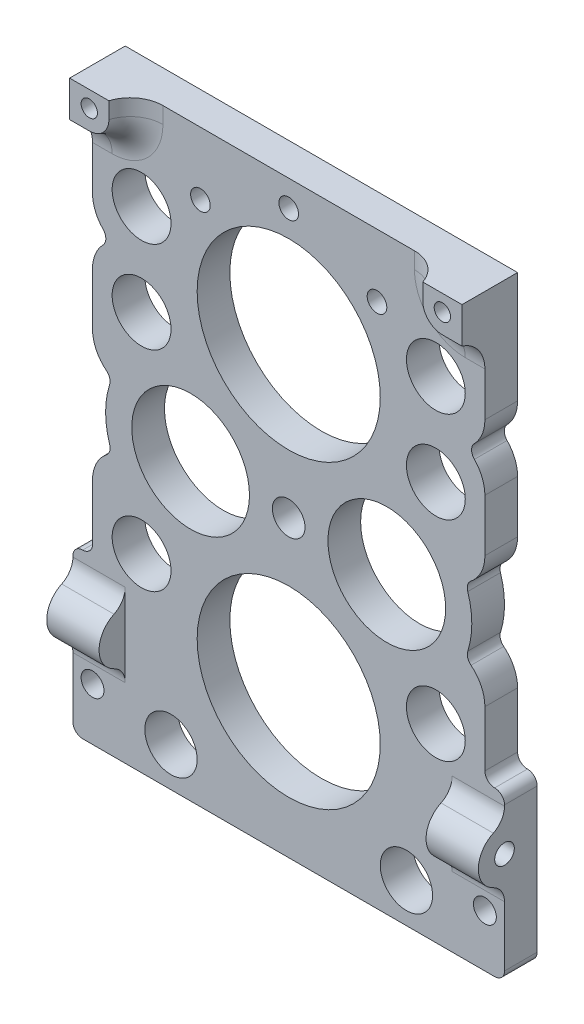
SolidWorks part; units mm, degrees
ref_plane "Front Plane" through (0, 0, 0) normal (0, 0, 1) x (1, 0, 0)
ref_plane "Top Plane" through (0, 0, 0) normal (0, 1, 0) x (1, 0, 0)
ref_plane "Right Plane" through (0, 0, 0) normal (1, 0, 0) x (0, 0, -1)
sketch "Sketch1" plane through (0, 0, 0) normal (0, 0, 1) x (1, 0, 0)
  line L1 (30, 45) -> (-30, 45)
  line L2 (30, 45) -> (30, -45)
  line L3 (30, -45) -> (-30, -45)
  line L4 (-30, 45) -> (-30, -45)
  line L5 (30, 45) -> (-30, -45) construction
  line L6 (30, -45) -> (-30, 45) construction
  point P0 (0, 0)
  dimension "D1" = 60
  dimension "D2" = 90
extrude "Boss-Extrude1" add sketch "Sketch1" along normal blind 5
sketch "Sketch2" plane through (30, 0, 0) normal (1, 0, 0) x (0, 0, -1)
  line L0 (0, -45) -> (0, 45) construction
  line L1 (-5, -45) -> (0, -45)
  line L2 (-5, -45) -> (-5, -20)
  line L3 (-5, -20) -> (0, -20)
  line L4 (0, -45) -> (0, -20)
  dimension "D1" = 25
extrude "Boss-Extrude2" add sketch "Sketch2" along normal blind 3
mirror "Mirror1" about plane through (0, 0, 0) normal (1, 0, 0) of "Boss-Extrude2"
sketch "Sketch3" plane through (0, 0, 5) normal (0, 0, 1) x (1, 0, 0)
  line L0 (0, 0) -> (0, 50000) construction
  line L1 (22.5, 13.0684) -> (22.5, -49986.9316) construction
  line L2 (-22.5, 11.0527) -> (-22.5, -49988.9473) construction
  line L3 (-15, 13.2998) -> (-15, -49986.7002) construction
  line L4 (15, 12.7972) -> (15, -49987.2028) construction
  line L5 (-1.6097, 0) -> (49998.3903, 0) construction
  line L6 (-5.4322, 16) -> (49994.5678, 16) construction
  line L7 (-7.793, 30) -> (49992.207, 30) construction
  line L8 (-33, -45) -> (33, -45) construction
  line L12 (0, 23) -> (-50000, 23) construction
  line L16 (30, -20) -> (30, 45) construction
  line L17 (30, -10) -> (30, 10)
  line L18 (30, 18) -> (30, 28)
  line L19 (27, 23) -> (27, -49977) construction
  line L21 (-30, 18) -> (-30, 28)
  line L22 (-30, -10) -> (-30, 10)
  circle A0 centre (0, -23) radius 14
  circle A1 centre (0, 23) radius 14
  circle A2 centre (15, 0) radius 9
  circle A3 centre (-15, 0) radius 9
  circle A4 centre (-22.5, -16) radius 4.5
  circle A5 centre (-18, -39) radius 4
  circle A6 centre (22.5, -16) radius 4.5
  circle A7 centre (18, -39) radius 4
  circle A10 centre (22.5, 16) radius 4.5
  circle A11 centre (22.5, 30) radius 4.5
  circle A12 centre (-22.5, 30) radius 4.5
  circle A13 centre (-22.5, 16) radius 4.5
  circle A14 centre (0, 0) radius 2.5
  arc A15 (30, 28) -> (27, 23) centre (24.3333, 28) cw
  arc A16 (30, 18) -> (27, 23) centre (24.3333, 18) ccw
  arc A17 (30, 10) -> (27, 5) centre (24.3333, 10) cw
  arc A18 (30, -10) -> (27, -5) centre (24.3333, -10) ccw
  arc A21 (27, -5) -> (27, 5) centre (15, 0) ccw
  arc A24 (-30, 28) -> (-27, 23) centre (-24.3333, 28) ccw
  arc A25 (-30, 18) -> (-27, 23) centre (-24.3333, 18) cw
  arc A26 (-30, -10) -> (-27, -5) centre (-24.3333, -10) cw
  arc A27 (-30, 10) -> (-27, 5) centre (-24.3333, 10) ccw
  arc A28 (-27, -5) -> (-27, 5) centre (-15, 0) cw
  point P3 (0, 0)
  dimension "D1" = 28
  dimension "D4" = 18
  dimension "D5" = 9
  dimension "D7" = 6
  dimension "D12" = 5
  dimension "D15" = 3
  dimension "D16" = 10
  dimension "D8" = 8
  dimension "D2" = 16
  dimension "D3" = 30
  dimension "D6" = 45
  dimension "D9" = 14
  dimension "D10" = 36
  dimension "D13" = 10
  dimension "D14" = 20
extrude "Cut-Extrude1" cut sketch "Sketch3" against normal through all
sketch "Sketch4" plane through (0, 0, 5) normal (0, 0, 1) x (1, 0, 0)
  line L0 (-33, -45) -> (33, -45) construction
  line L1 (0, 0) -> (0, -50000) construction
  line L2 (-33, -37) -> (49967, -37) construction
  circle A0 centre (-30, -37) radius 1.75
  circle A1 centre (30, -37) radius 1.75
  dimension "D1" = 3.5
  dimension "D2" = 60
  dimension "D3" = 8
extrude "Cut-Extrude2" cut sketch "Sketch4" against normal through all
fillet "Fillet1" radius 1.5 6 edges at (-33, -45, 2.5) (-33, -20, 2.5) (33, -45, 2.5) (33, -20, 2.5)
fillet "Fillet2" radius 1.5 6 edges at (27, -5, 2.5) (27, 5, 2.5) (27, 23, 2.5) (-27, -5, 2.5) (-27, 5, 2.5) (-27, 23, 2.5)
sketch "Sketch5" plane through (0, 0, 5) normal (0, 0, 1) x (1, 0, 0)
  line L0 (24, 45) -> (30, 45)
  line L1 (30, 45) -> (-30, 45) construction
  line L2 (30, 45) -> (30, 39.5)
  line L3 (30, 28) -> (30, 45) construction
  line L4 (30, 39.5) -> (27, 39.5)
  line L5 (24, 45) -> (24, 42.5)
  arc A0 (27, 39.5) -> (24, 42.5) centre (27, 42.5) cw
  dimension "D1" = 3
extrude "Boss-Extrude3" add sketch "Sketch5" along normal up to surface (3.5 mm away) up to face at (28.25, -37, 0)
sketch "Sketch6" plane through (0, 0, 8.5) normal (0, 0, 1) x (1, 0, 0)
  circle A0 centre (27, 42.5) radius 1.25
  dimension "D1" = 2.5
extrude "Cut-Extrude3" cut sketch "Sketch6" against normal through all
fillet "Fillet3" radius 5 3 edges at (24, 43.75, 5) (24.8787, 40.3787, 5) (28.5, 39.5, 5)
mirror "Mirror2" about plane through (0, 0, 0) normal (1, 0, 0) of "Fillet3", "Boss-Extrude3", "Cut-Extrude3"
sketch "Sketch12" plane through (0, 0, 0) normal (0, 0, -1) x (-1, 0, 0)
  circle A0 centre (-13.5, 35.3697) radius 1.5
  circle A2 centre (0, 41) radius 1.5
  circle A4 centre (13.5, 35.3697) radius 1.5
  dimension "D1" = 3
extrude "Cut-Extrude7" cut sketch "Sketch12" against normal through all
sketch "Sketch14" plane through (33, 0, 0) normal (1, 0, 0) x (0, 0, -1)
  line L0 (-5, -24) -> (-5, -32)
  line L1 (-5, -21.5) -> (-5, -43.5) construction
  arc A0 (-5, -32) -> (-5, -24) centre (-5, -28) cw
  dimension "D1" = 8
  dimension "D2" = 13
extrude "Boss-Extrude5" add sketch "Sketch14" against normal blind 8
fillet "Fillet5" radius 3 2 edges at (29, -24, 5) (29, -32, 5)
sketch "Sketch15" plane through (33, 0, 0) normal (1, 0, 0) x (0, 0, -1)
  circle A0 centre (-5, -28) radius 1.5
  dimension "D1" = 3
extrude "Cut-Extrude8" cut sketch "Sketch15" against normal blind 5
mirror "Mirror3" about plane through (0, 0, 0) normal (1, 0, 0) of "Cut-Extrude8", "Fillet5", "Boss-Extrude5"
